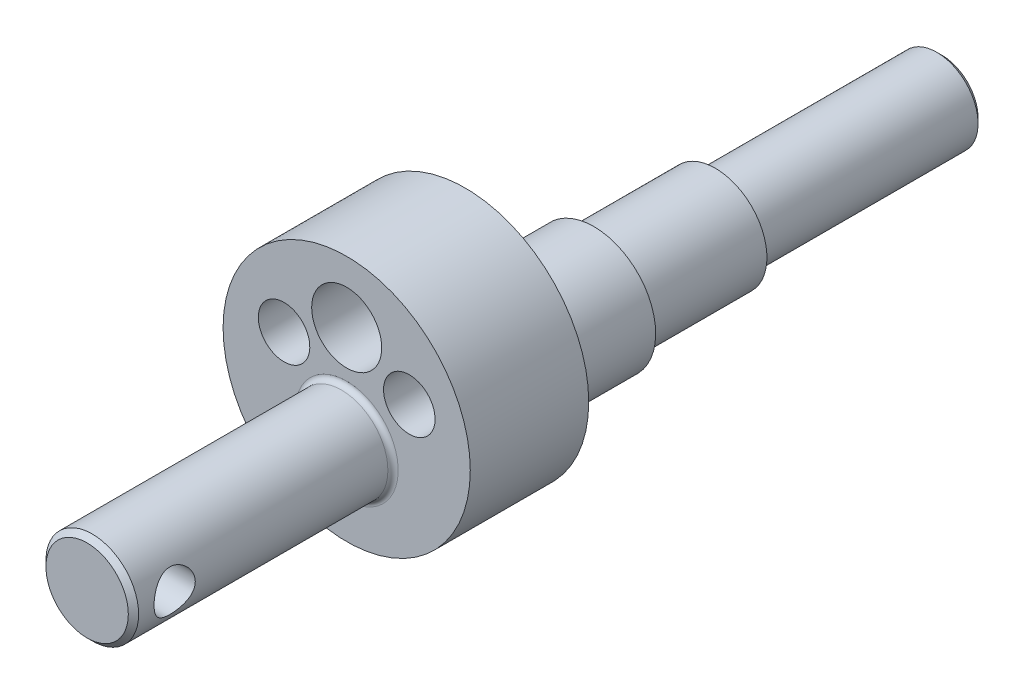
SolidWorks part; units mm, degrees
other "DetailItem1"
extrude "Boss-Extrude4" add sketch "Sketch8" along normal blind 8
sketch "Sketch8" plane through (0, 0, -61) normal (0, 0, -1) x (-1, 0, 0)
  circle A0 centre (0, 0) radius 4
  dimension "D1" = 8
extrude "Boss-Extrude3" add sketch "Sketch6" along normal blind 11.8
sketch "Sketch6" plane through (0, 0, -49.2) normal (0, 0, -1) x (-1, 0, 0)
  circle A0 centre (0, 0) radius 5
  dimension "D1" = 10
extrude "Boss-Extrude8" add sketch "Sketch9" along normal blind 14
sketch "Sketch9" plane through (0, 0, -69) normal (0, 0, -1) x (-1, 0, 0)
  circle A0 centre (0, 0) radius 4
  dimension "D1" = 8
extrude "Base-Extrude" add sketch "Sketch1" against normal blind 25.2
sketch "Sketch1" plane through (0, 0, 0) normal (0, 0, 1) x (1, 0, 0)
  circle A0 centre (0, 0) radius 4.5
  point P3 (-4.5, 0)
  dimension "D1" = 9
extrude "Boss-Extrude1" add sketch "Sketch2" along normal blind 11.5
sketch "Sketch2" plane through (0, 0, -25.2) normal (0, 0, -1) x (-1, 0, 0)
  line L0 (0, 0) -> (0, 20.9808) construction
  line L1 (0, 0) -> (17.5425, 17.5425) construction
  line L2 (0, 0) -> (-15.9043, 15.9043) construction
  circle A0 centre (0, 9.5) radius 3.4
  circle A1 centre (0, 3.5) radius 12
  circle A2 centre (6.0811, 6.0811) radius 2.5
  circle A3 centre (-6.0811, 6.0811) radius 2.5
  point P0 (0, 3.5)
  point P3 (0, 9.5)
  point P5 (6.0811, 6.0811)
  point P6 (-6.0811, 6.0811)
  dimension "D2" = 24
  dimension "D8" = 6.8
  dimension "D9" = 5
  dimension "D10" = 5
  dimension "D1" = 3.5
  dimension "D3" = 6
  dimension "D4" = 45
  dimension "D5" = 45
  dimension "D6" = 8.6
  dimension "D7" = 8.6
extrude "Boss-Extrude2" add sketch "Sketch3" along normal blind 12.5
sketch "Sketch3" plane through (0, 0, -36.7) normal (0, 0, -1) x (-1, 0, 0)
  circle A0 centre (0, 0) radius 6
  dimension "D1" = 12
ref_plane "Front" through (0, 0, 0) normal (0, 0, 1) x (1, 0, 0)
ref_plane "Top" through (0, 0, 0) normal (0, 1, 0) x (1, 0, 0)
ref_plane "Right" through (0, 0, 0) normal (1, 0, 0) x (0, 0, -1)
ref_plane "Plane1" through (0, 0, -25.2) normal (0, 0, -1) x (-1, 0, 0)
ref_plane "Plane2" through (0, 0, -36.7) normal (0, 0, -1) x (-1, 0, 0)
ref_plane "Plane3" through (4.5, 0, 0) normal (1, 0, 0) x (0, 0, -1)
sketch "Sketch4" plane through (4.5, 0, 0) normal (1, 0, 0) x (0, 0, -1)
  line L0 (25.2, 0) -> (0, 0) construction
  circle A0 centre (4, 0) radius 2
  point P0 (4, 0)
  dimension "D2" = 4
  dimension "D1" = 4
extrude "Cut-Extrude1" cut sketch "Sketch4" against normal through all
ref_plane "Plane4" through (0, 0, -49.2) normal (0, 0, -1) x (-1, 0, 0)
ref_plane "Plane5" through (0, -5, 0) normal (0, 1, 0) x (-1, 0, 0)
sketch "Sketch7" plane through (0, -5, 0) normal (0, 1, 0) x (-1, 0, 0)
  line L0 (0, -25.2) -> (0, 0) construction
  line L1 (-5, -61) -> (5, -61) construction
  line L2 (-1.5, -52.5) -> (-1.5, -58.5)
  line L3 (1.5, -52.5) -> (1.5, -58.5)
  arc A0 (1.5, -52.5) -> (-1.5, -52.5) centre (0, -52.5) ccw
  arc A1 (-1.5, -58.5) -> (1.5, -58.5) centre (0, -58.5) ccw
  point P0 (0, -58.5)
  point P5 (0, -52.5)
  dimension "D3" = 1.5
  dimension "D4" = 3
  dimension "D1" = 2.5
  dimension "D2" = 6
extrude "Cut-Extrude2" cut sketch "Sketch7" along normal blind 1.5
ref_plane "Plane6" through (0, 0, -61) normal (0, 0, -1) x (-1, 0, 0)
ref_plane "Plane7" through (0, 0, -69) normal (0, 0, -1) x (-1, 0, 0)
chamfer "Chamfer1" distance 0.5 angle 45 1 edges at (-4, 0, -83)
fillet "Fillet1" radius 0.5 1 edges at (-4.5, 0, -25.2)
fillet "Fillet2" radius 0.5 1 edges at (-6, 0, -36.7)
fillet "Fillet3" radius 0.5 1 edges at (-5, 0, -49.2)
fillet "Fillet4" radius 0.5 1 edges at (-4, 0, -61)
chamfer "Chamfer2" distance 0.5 angle 45 1 edges at (4.5, 0, 0)
